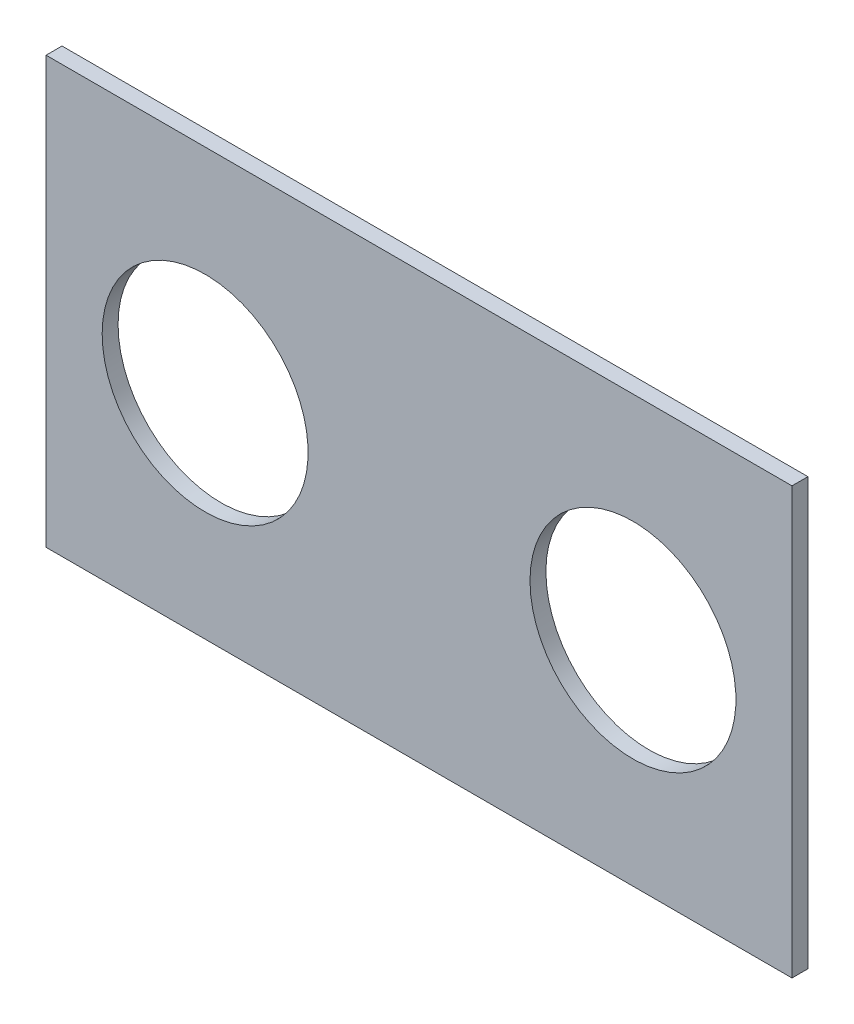
SolidWorks part; units mm, degrees
material "Plain Carbon Steel"
ref_plane "Front Plane" through (0, 0, 0) normal (0, 0, 1) x (1, 0, 0)
ref_plane "Top Plane" through (0, 0, 0) normal (0, 1, 0) x (1, 0, 0)
ref_plane "Right Plane" through (0, 0, 0) normal (1, 0, 0) x (0, 0, -1)
sketch "Sketch1" plane through (0, 0, 0) normal (0, 0, 1) x (1, 0, 0)
  line L1 (-18.9548, 25.4) -> (69.9452, 25.4)
  line L2 (-18.9548, 25.4) -> (-18.9548, -25.4)
  line L3 (-18.9548, -25.4) -> (69.9452, -25.4)
  line L4 (69.9452, 25.4) -> (69.9452, -25.4)
  circle A0 centre (0, 0) radius 12.2726
  circle A1 centre (50.9905, 0) radius 12.2726
  circle A2 centre (50.9905, 0) radius 12.2726 construction
  circle A3 centre (0, 0) radius 12.2726 construction
extrude "Boss-Extrude1" add sketch "Sketch1" along normal blind 1.8974
